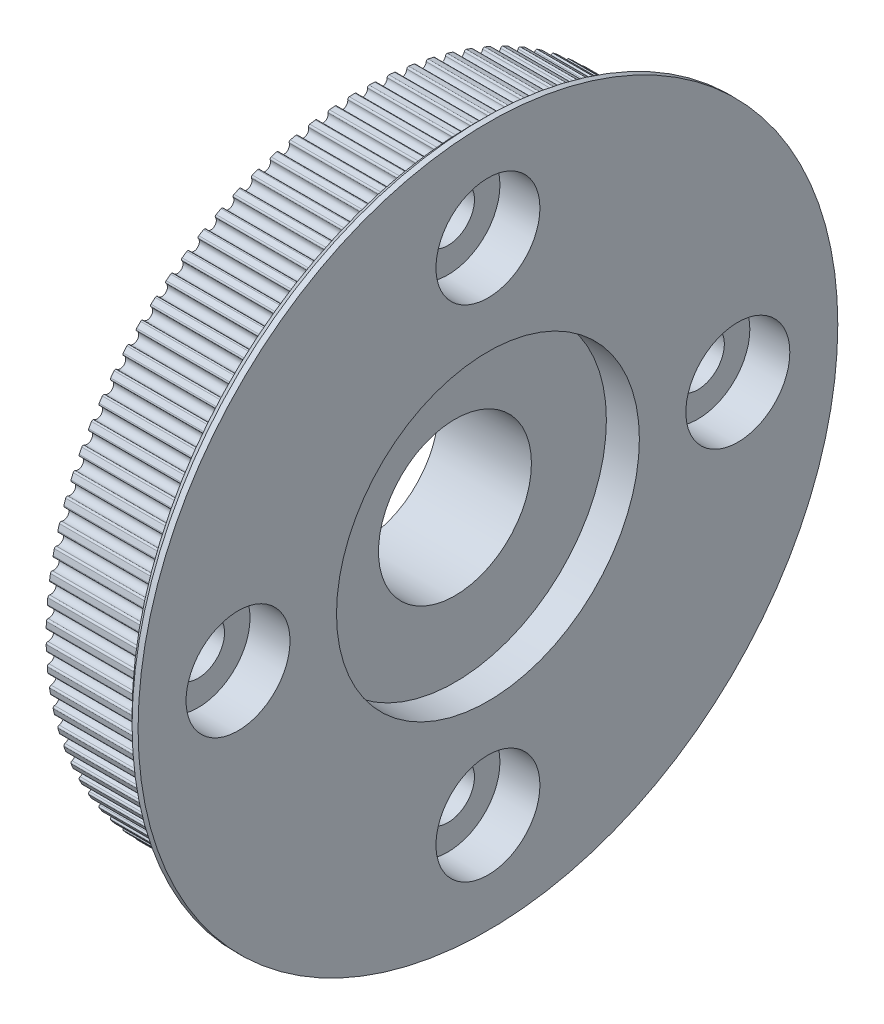
SolidWorks part; units mm, degrees
ref_plane "Front Plane" through (0, 0, 0) normal (0, 0, 1) x (1, 0, 0)
ref_plane "Top Plane" through (0, 0, 0) normal (0, 1, 0) x (1, 0, 0)
ref_plane "Right Plane" through (0, 0, 0) normal (1, 0, 0) x (0, 0, -1)
sketch "Sketch1" plane through (0, 0, 0) normal (1, 0, 0) x (0, 0, -1)
  circle A0 centre (0, 0) radius 31.6
  circle A1 centre (0, 0) radius 7.65
  dimension "D1" = 63.2
  dimension "D2" = 15.3
extrude "Boss-Extrude1" add sketch "Sketch1" along normal blind 11
sketch "Sketch2" plane through (0, 0, 0) normal (1, 0, 0) x (0, 0, -1)
  circle A0 centre (0, 0) radius 31.39 construction
  circle A1 centre (0, 31.39) radius 0.55
  circle A2 centre (0, 0) radius 31.39 construction
  circle A3 centre (1.971, 31.3281) radius 0.55
  circle A4 centre (0, 0) radius 31.39 construction
  circle A5 centre (3.9342, 31.1425) radius 0.55
  circle A6 centre (0, 0) radius 31.39 construction
  circle A7 centre (5.8819, 30.834) radius 0.55
  circle A8 centre (0, 0) radius 31.39 construction
  circle A9 centre (7.8064, 30.4038) radius 0.55
  circle A10 centre (0, 0) radius 31.39 construction
  circle A11 centre (9.7, 29.8537) radius 0.55
  circle A12 centre (0, 0) radius 31.39 construction
  circle A13 centre (11.5554, 29.1857) radius 0.55
  circle A14 centre (0, 0) radius 31.39 construction
  circle A15 centre (13.3652, 28.4025) radius 0.55
  circle A16 centre (0, 0) radius 31.39 construction
  circle A17 centre (15.1222, 27.5073) radius 0.55
  circle A18 centre (0, 0) radius 31.39 construction
  circle A19 centre (16.8196, 26.5035) radius 0.55
  circle A20 centre (0, 0) radius 31.39 construction
  circle A21 centre (18.4506, 25.395) radius 0.55
  circle A22 centre (0, 0) radius 31.39 construction
  circle A23 centre (20.0087, 24.1864) radius 0.55
  circle A24 centre (0, 0) radius 31.39 construction
  circle A25 centre (21.4879, 22.8823) radius 0.55
  circle A26 centre (0, 0) radius 31.39 construction
  circle A27 centre (22.8823, 21.4879) radius 0.55
  circle A28 centre (0, 0) radius 31.39 construction
  circle A29 centre (24.1864, 20.0087) radius 0.55
  circle A30 centre (0, 0) radius 31.39 construction
  circle A31 centre (25.395, 18.4506) radius 0.55
  circle A32 centre (0, 0) radius 31.39 construction
  circle A33 centre (26.5035, 16.8196) radius 0.55
  circle A34 centre (0, 0) radius 31.39 construction
  circle A35 centre (27.5073, 15.1222) radius 0.55
  circle A36 centre (0, 0) radius 31.39 construction
  circle A37 centre (28.4025, 13.3652) radius 0.55
  circle A38 centre (0, 0) radius 31.39 construction
  circle A39 centre (29.1857, 11.5554) radius 0.55
  circle A40 centre (0, 0) radius 31.39 construction
  circle A41 centre (29.8537, 9.7) radius 0.55
  circle A42 centre (0, 0) radius 31.39 construction
  circle A43 centre (30.4038, 7.8064) radius 0.55
  circle A44 centre (0, 0) radius 31.39 construction
  circle A45 centre (30.834, 5.8819) radius 0.55
  circle A46 centre (0, 0) radius 31.39 construction
  circle A47 centre (31.1425, 3.9342) radius 0.55
  circle A48 centre (0, 0) radius 31.39 construction
  circle A49 centre (31.3281, 1.971) radius 0.55
  circle A50 centre (0, 0) radius 31.39 construction
  circle A51 centre (31.39, 0) radius 0.55
  circle A52 centre (0, 0) radius 31.39 construction
  circle A53 centre (31.3281, -1.971) radius 0.55
  circle A54 centre (0, 0) radius 31.39 construction
  circle A55 centre (31.1425, -3.9342) radius 0.55
  circle A56 centre (0, 0) radius 31.39 construction
  circle A57 centre (30.834, -5.8819) radius 0.55
  circle A58 centre (0, 0) radius 31.39 construction
  circle A59 centre (30.4038, -7.8064) radius 0.55
  circle A60 centre (0, 0) radius 31.39 construction
  circle A61 centre (29.8537, -9.7) radius 0.55
  circle A62 centre (0, 0) radius 31.39 construction
  circle A63 centre (29.1857, -11.5554) radius 0.55
  circle A64 centre (0, 0) radius 31.39 construction
  circle A65 centre (28.4025, -13.3652) radius 0.55
  circle A66 centre (0, 0) radius 31.39 construction
  circle A67 centre (27.5073, -15.1222) radius 0.55
  circle A68 centre (0, 0) radius 31.39 construction
  circle A69 centre (26.5035, -16.8196) radius 0.55
  circle A70 centre (0, 0) radius 31.39 construction
  circle A71 centre (25.395, -18.4506) radius 0.55
  circle A72 centre (0, 0) radius 31.39 construction
  circle A73 centre (24.1864, -20.0087) radius 0.55
  circle A74 centre (0, 0) radius 31.39 construction
  circle A75 centre (22.8823, -21.4879) radius 0.55
  circle A76 centre (0, 0) radius 31.39 construction
  circle A77 centre (21.4879, -22.8823) radius 0.55
  circle A78 centre (0, 0) radius 31.39 construction
  circle A79 centre (20.0087, -24.1864) radius 0.55
  circle A80 centre (0, 0) radius 31.39 construction
  circle A81 centre (18.4506, -25.395) radius 0.55
  circle A82 centre (0, 0) radius 31.39 construction
  circle A83 centre (16.8196, -26.5035) radius 0.55
  circle A84 centre (0, 0) radius 31.39 construction
  circle A85 centre (15.1222, -27.5073) radius 0.55
  circle A86 centre (0, 0) radius 31.39 construction
  circle A87 centre (13.3652, -28.4025) radius 0.55
  circle A88 centre (0, 0) radius 31.39 construction
  circle A89 centre (11.5554, -29.1857) radius 0.55
  circle A90 centre (0, 0) radius 31.39 construction
  circle A91 centre (9.7, -29.8537) radius 0.55
  circle A92 centre (0, 0) radius 31.39 construction
  circle A93 centre (7.8064, -30.4038) radius 0.55
  circle A94 centre (0, 0) radius 31.39 construction
  circle A95 centre (5.8819, -30.834) radius 0.55
  circle A96 centre (0, 0) radius 31.39 construction
  circle A97 centre (3.9342, -31.1425) radius 0.55
  circle A98 centre (0, 0) radius 31.39 construction
  circle A99 centre (1.971, -31.3281) radius 0.55
  circle A100 centre (0, 0) radius 31.39 construction
  circle A101 centre (0, -31.39) radius 0.55
  circle A102 centre (0, 0) radius 31.39 construction
  circle A103 centre (-1.971, -31.3281) radius 0.55
  circle A104 centre (0, 0) radius 31.39 construction
  circle A105 centre (-3.9342, -31.1425) radius 0.55
  circle A106 centre (0, 0) radius 31.39 construction
  circle A107 centre (-5.8819, -30.834) radius 0.55
  circle A108 centre (0, 0) radius 31.39 construction
  circle A109 centre (-7.8064, -30.4038) radius 0.55
  circle A110 centre (0, 0) radius 31.39 construction
  circle A111 centre (-9.7, -29.8537) radius 0.55
  circle A112 centre (0, 0) radius 31.39 construction
  circle A113 centre (-11.5554, -29.1857) radius 0.55
  circle A114 centre (0, 0) radius 31.39 construction
  circle A115 centre (-13.3652, -28.4025) radius 0.55
  circle A116 centre (0, 0) radius 31.39 construction
  circle A117 centre (-15.1222, -27.5073) radius 0.55
  circle A118 centre (0, 0) radius 31.39 construction
  circle A119 centre (-16.8196, -26.5035) radius 0.55
  circle A120 centre (0, 0) radius 31.39 construction
  circle A121 centre (-18.4506, -25.395) radius 0.55
  circle A122 centre (0, 0) radius 31.39 construction
  circle A123 centre (-20.0087, -24.1864) radius 0.55
  circle A124 centre (0, 0) radius 31.39 construction
  circle A125 centre (-21.4879, -22.8823) radius 0.55
  circle A126 centre (0, 0) radius 31.39 construction
  circle A127 centre (-22.8823, -21.4879) radius 0.55
  circle A128 centre (0, 0) radius 31.39 construction
  circle A129 centre (-24.1864, -20.0087) radius 0.55
  circle A130 centre (0, 0) radius 31.39 construction
  circle A131 centre (-25.395, -18.4506) radius 0.55
  circle A132 centre (0, 0) radius 31.39 construction
  circle A133 centre (-26.5035, -16.8196) radius 0.55
  circle A134 centre (0, 0) radius 31.39 construction
  circle A135 centre (-27.5073, -15.1222) radius 0.55
  circle A136 centre (0, 0) radius 31.39 construction
  circle A137 centre (-28.4025, -13.3652) radius 0.55
  circle A138 centre (0, 0) radius 31.39 construction
  circle A139 centre (-29.1857, -11.5554) radius 0.55
  circle A140 centre (0, 0) radius 31.39 construction
  circle A141 centre (-29.8537, -9.7) radius 0.55
  circle A142 centre (0, 0) radius 31.39 construction
  circle A143 centre (-30.4038, -7.8064) radius 0.55
  circle A144 centre (0, 0) radius 31.39 construction
  circle A145 centre (-30.834, -5.8819) radius 0.55
  circle A146 centre (0, 0) radius 31.39 construction
  circle A147 centre (-31.1425, -3.9342) radius 0.55
  circle A148 centre (0, 0) radius 31.39 construction
  circle A149 centre (-31.3281, -1.971) radius 0.55
  circle A150 centre (0, 0) radius 31.39 construction
  circle A151 centre (-31.39, 0) radius 0.55
  circle A152 centre (0, 0) radius 31.39 construction
  circle A153 centre (-31.3281, 1.971) radius 0.55
  circle A154 centre (0, 0) radius 31.39 construction
  circle A155 centre (-31.1425, 3.9342) radius 0.55
  circle A156 centre (0, 0) radius 31.39 construction
  circle A157 centre (-30.834, 5.8819) radius 0.55
  circle A158 centre (0, 0) radius 31.39 construction
  circle A159 centre (-30.4038, 7.8064) radius 0.55
  circle A160 centre (0, 0) radius 31.39 construction
  circle A161 centre (-29.8537, 9.7) radius 0.55
  circle A162 centre (0, 0) radius 31.39 construction
  circle A163 centre (-29.1857, 11.5554) radius 0.55
  circle A164 centre (0, 0) radius 31.39 construction
  circle A165 centre (-28.4025, 13.3652) radius 0.55
  circle A166 centre (0, 0) radius 31.39 construction
  circle A167 centre (-27.5073, 15.1222) radius 0.55
  circle A168 centre (0, 0) radius 31.39 construction
  circle A169 centre (-26.5035, 16.8196) radius 0.55
  circle A170 centre (0, 0) radius 31.39 construction
  circle A171 centre (-25.395, 18.4506) radius 0.55
  circle A172 centre (0, 0) radius 31.39 construction
  circle A173 centre (-24.1864, 20.0087) radius 0.55
  circle A174 centre (0, 0) radius 31.39 construction
  circle A175 centre (-22.8823, 21.4879) radius 0.55
  circle A176 centre (0, 0) radius 31.39 construction
  circle A177 centre (-21.4879, 22.8823) radius 0.55
  circle A178 centre (0, 0) radius 31.39 construction
  circle A179 centre (-20.0087, 24.1864) radius 0.55
  circle A180 centre (0, 0) radius 31.39 construction
  circle A181 centre (-18.4506, 25.395) radius 0.55
  circle A182 centre (0, 0) radius 31.39 construction
  circle A183 centre (-16.8196, 26.5035) radius 0.55
  circle A184 centre (0, 0) radius 31.39 construction
  circle A185 centre (-15.1222, 27.5073) radius 0.55
  circle A186 centre (0, 0) radius 31.39 construction
  circle A187 centre (-13.3652, 28.4025) radius 0.55
  circle A188 centre (0, 0) radius 31.39 construction
  circle A189 centre (-11.5554, 29.1857) radius 0.55
  circle A190 centre (0, 0) radius 31.39 construction
  circle A191 centre (-9.7, 29.8537) radius 0.55
  circle A192 centre (0, 0) radius 31.39 construction
  circle A193 centre (-7.8064, 30.4038) radius 0.55
  circle A194 centre (0, 0) radius 31.39 construction
  circle A195 centre (-5.8819, 30.834) radius 0.55
  circle A196 centre (0, 0) radius 31.39 construction
  circle A197 centre (-3.9342, 31.1425) radius 0.55
  circle A198 centre (0, 0) radius 31.39 construction
  circle A199 centre (-1.971, 31.3281) radius 0.55
  point P305 (0, 0)
  dimension "D1" = 62.78
  dimension "D2" = 1.1
  dimension "D3" = 100
extrude "Cut-Extrude1" cut sketch "Sketch2" along normal up to surface (11 mm away) up to face at (11, 0, -31.6)
fillet "Fillet1" radius 0.16 200 edges at (5.5, 31.5959, 0.51) (5.5, 31.5656, 1.4749) (5.5, 21.2571, -23.3815) (5.5, 22.6833, -22.0007) (5.5, 22.0007, -22.6833) (5.5, 20.5329, -24.02) (5.5, 19.747, -24.6701) (5.5, 18.9842, -25.2618) (5.5, 18.159, -25.8614) (5.5, 17.3605, -26.404) (5.5, 16.4993, -26.9506) (5.5, 15.6684, -27.442) (5.5, 14.7745, -27.9334) (5.5, 13.9143, -28.3717) (5.5, 12.9914, -28.806) (5.5, 12.1054, -29.1894) (5.5, 23.3815, -21.2571) (5.5, 24.02, -20.5329) (5.5, 24.6701, -19.747) (5.5, 25.2618, -18.9842) (5.5, 25.8614, -18.159) (5.5, 26.404, -17.3605) (5.5, 26.9506, -16.4993) (5.5, 27.442, -15.6684) (5.5, 27.9334, -14.7745) (5.5, 28.3717, -13.9143) (5.5, 28.806, -12.9914) (5.5, 29.1894, -12.1054) (5.5, 29.5649, -11.157) (5.5, 29.8919, -10.2487) (5.5, 30.2071, -9.2786) (5.5, 30.4764, -8.3516) (5.5, 30.7301, -7.3636) (5.5, 30.9407, -6.4215) (5.5, 31.1318, -5.4195) (5.5, 31.2828, -4.466) (5.5, 31.4107, -3.454) (5.5, 31.5015, -2.4929) (5.5, 31.5656, -1.4749) (5.5, 31.5959, -0.51) (5.5, 31.5015, 2.4929) (5.5, 31.4107, 3.454) (5.5, 31.2828, 4.466) (5.5, 31.1318, 5.4195) (5.5, 30.9407, 6.4215) (5.5, 30.7301, 7.3636) (5.5, 30.4764, 8.3516) (5.5, 30.2071, 9.2786) (5.5, 29.8919, 10.2487) (5.5, 29.5649, 11.157) (5.5, 29.1894, 12.1054) (5.5, 28.806, 12.9914) (5.5, 28.3717, 13.9143) (5.5, 27.9334, 14.7745) (5.5, 27.442, 15.6684) (5.5, 26.9506, 16.4993) (5.5, 26.404, 17.3605) (5.5, 25.8614, 18.159) (5.5, 25.2618, 18.9842) (5.5, 24.6701, 19.747) (5.5, 24.02, 20.5329) (5.5, 23.3815, 21.2571) (5.5, 22.6833, 22.0007) (5.5, 22.0007, 22.6833) (5.5, 21.2571, 23.3815) (5.5, 20.5329, 24.02) (5.5, 19.747, 24.6701) (5.5, 18.9842, 25.2618) (5.5, 18.159, 25.8614) (5.5, 17.3605, 26.404) (5.5, 16.4993, 26.9506) (5.5, 15.6684, 27.442) (5.5, 14.7745, 27.9334) (5.5, 13.9143, 28.3717) (5.5, 12.9914, 28.806) (5.5, 12.1054, 29.1894) (5.5, 11.157, 29.5649) (5.5, 10.2487, 29.8919) (5.5, 9.2786, 30.2071) (5.5, 8.3516, 30.4764) (5.5, 7.3636, 30.7301) (5.5, 6.4215, 30.9407) (5.5, 5.4195, 31.1318) (5.5, 4.466, 31.2828) (5.5, 3.454, 31.4107) (5.5, 2.4929, 31.5015) (5.5, 1.4749, 31.5656) (5.5, 0.51, 31.5959) (5.5, -0.51, 31.5959) (5.5, -1.4749, 31.5656) (5.5, -2.4929, 31.5015) (5.5, -3.454, 31.4107) (5.5, -4.466, 31.2828) (5.5, -5.4195, 31.1318) (5.5, -6.4215, 30.9407) (5.5, -7.3636, 30.7301) (5.5, -8.3516, 30.4764) (5.5, -9.2786, 30.2071) (5.5, -10.2487, 29.8919) (5.5, -11.157, 29.5649) (5.5, -12.1054, 29.1894) (5.5, -12.9914, 28.806) (5.5, -13.9143, 28.3717) (5.5, -14.7745, 27.9334) (5.5, -15.6684, 27.442) (5.5, -16.4993, 26.9506) (5.5, -17.3605, 26.404) (5.5, -18.159, 25.8614) (5.5, -18.9842, 25.2618) (5.5, -19.747, 24.6701) (5.5, -20.5329, 24.02) (5.5, -21.2571, 23.3815) (5.5, -22.0007, 22.6833) (5.5, -22.6833, 22.0007) (5.5, -23.3815, 21.2571) (5.5, -24.02, 20.5329) (5.5, -24.6701, 19.747) (5.5, -25.2618, 18.9842) (5.5, -25.8614, 18.159) (5.5, -26.404, 17.3605) (5.5, -26.9506, 16.4993) (5.5, -27.442, 15.6684) (5.5, -27.9334, 14.7745) (5.5, -28.3717, 13.9143) (5.5, -28.806, 12.9914) (5.5, -29.1894, 12.1054) (5.5, -29.5649, 11.157) (5.5, -29.8919, 10.2487) (5.5, -30.2071, 9.2786) (5.5, -30.4764, 8.3516) (5.5, -30.7301, 7.3636) (5.5, -30.9407, 6.4215) (5.5, -31.1318, 5.4195) (5.5, -31.2828, 4.466) (5.5, -31.4107, 3.454) (5.5, -31.5015, 2.4929) (5.5, -31.5656, 1.4749) (5.5, -31.5959, 0.51) (5.5, -31.5959, -0.51) (5.5, -31.5656, -1.4749) (5.5, -31.5015, -2.4929) (5.5, -31.4107, -3.454) (5.5, -31.2828, -4.466) (5.5, -31.1318, -5.4195) (5.5, -30.9407, -6.4215) (5.5, -30.7301, -7.3636) (5.5, -30.4764, -8.3516) (5.5, -30.2071, -9.2786) (5.5, -29.8919, -10.2487) (5.5, -29.5649, -11.157) (5.5, -29.1894, -12.1054) (5.5, -28.806, -12.9914) (5.5, -28.3717, -13.9143) (5.5, -27.9334, -14.7745) (5.5, -27.442, -15.6684) (5.5, -26.9506, -16.4993) (5.5, -26.404, -17.3605) (5.5, -25.8614, -18.159) (5.5, -25.2618, -18.9842) (5.5, -24.6701, -19.747) (5.5, -24.02, -20.5329) (5.5, -23.3815, -21.2571) (5.5, -22.6833, -22.0007) (5.5, -22.0007, -22.6833) (5.5, -21.2571, -23.3815) (5.5, -20.5329, -24.02) (5.5, -19.747, -24.6701) (5.5, -18.9842, -25.2618) (5.5, -18.159, -25.8614) (5.5, -17.3605, -26.404) (5.5, -16.4993, -26.9506) (5.5, -15.6684, -27.442) (5.5, -14.7745, -27.9334) (5.5, -13.9143, -28.3717) (5.5, -12.9914, -28.806) (5.5, -12.1054, -29.1894) (5.5, -11.157, -29.5649) (5.5, -10.2487, -29.8919) (5.5, -9.2786, -30.2071) (5.5, -8.3516, -30.4764) (5.5, -7.3636, -30.7301) (5.5, -6.4215, -30.9407) (5.5, -5.4195, -31.1318) (5.5, -4.466, -31.2828) (5.5, -3.454, -31.4107) (5.5, -2.4929, -31.5015) (5.5, 11.157, -29.5649) (5.5, 10.2487, -29.8919) (5.5, 9.2786, -30.2071) (5.5, 8.3516, -30.4764) (5.5, 7.3636, -30.7301) (5.5, 6.4215, -30.9407) (5.5, 5.4195, -31.1318) (5.5, 4.466, -31.2828) (5.5, 3.454, -31.4107) (5.5, 2.4929, -31.5015) (5.5, 1.4749, -31.5656) (5.5, 0.51, -31.5959) (5.5, -1.4749, -31.5656) (5.5, -0.51, -31.5959)
sketch "Sketch3" plane through (11, 0, 0) normal (1, 0, 0) x (0, 0, -1)
  circle A0 centre (0, 0) radius 35
  circle A1 centre (0, 0) radius 7.65
  circle A2 centre (0, 0) radius 7.65 construction
  dimension "D1" = 70
extrude "Boss-Extrude2" add sketch "Sketch3" along normal blind 1.6
chamfer "Chamfer1" distance 1 angle 45 1 edges at (11, 0, -35)
sketch "Sketch8" plane through (12.6, 0, 0) normal (1, 0, 0) x (0, 0, -1)
  circle A0 centre (0, 0) radius 15.15
  dimension "D1" = 30.3
extrude "Cut-Extrude7" cut sketch "Sketch8" against normal blind 3.3
sketch "Croquis2" plane through (9.3, 0, 0) normal (1, 0, 0) x (0, 0, -1)
  circle A0 centre (0, 0) radius 15.15
  dimension "D1" = 30.3
extrude "Saliente-Extruir1" add sketch "Croquis2" against normal up to vertex (9.3 mm away) up to point (0, -21.1069, -23.5172)
sketch "Croquis3" plane through (9.3, 0, 0) normal (1, 0, 0) x (0, 0, -1)
  circle A0 centre (0, 0) radius 7.65
  dimension "D1" = 15.3
extrude "Cortar-Extruir1" cut sketch "Croquis3" against normal through all
sketch "Croquis6" plane through (12.6, 0, 0) normal (1, 0, 0) x (0, 0, -1)
  line L0 (0, 0) -> (0, -25) construction
  line L1 (0, 0) -> (25, 0) construction
  line L2 (0, 0) -> (-25, 0) construction
  line L3 (0, 0) -> (0, 25) construction
  circle A0 centre (0, -25) radius 5.2
  circle A1 centre (25, 0) radius 5.2
  circle A2 centre (-25, 0) radius 5.2
  circle A3 centre (0, 25) radius 5.2
  dimension "D5" = 10.4
  dimension "D1" = 25
  dimension "D2" = 25
  dimension "D3" = 25
  dimension "D4" = 25
extrude "Cortar-Extruir2" cut sketch "Croquis6" against normal blind 4
sketch "Croquis7" plane through (8.6, 0, 0) normal (1, 0, 0) x (0, 0, -1)
  circle A0 centre (0, -25) radius 2.65
  dimension "D1" = 5.3
extrude "Cortar-Extruir3" cut sketch "Croquis7" against normal through all
sketch "Croquis8" plane through (8.6, 0, 0) normal (1, 0, 0) x (0, 0, -1)
  circle A0 centre (-25, 0) radius 2.65
  dimension "D1" = 5.3
extrude "Cortar-Extruir4" cut sketch "Croquis8" against normal through all
sketch "Croquis9" plane through (8.6, 0, 0) normal (1, 0, 0) x (0, 0, -1)
  circle A0 centre (25, 0) radius 2.65
  dimension "D1" = 5.3
extrude "Cortar-Extruir5" cut sketch "Croquis9" against normal through all
sketch "Croquis10" plane through (8.6, 0, 0) normal (1, 0, 0) x (0, 0, -1)
  circle A0 centre (0, 25) radius 2.65
  dimension "D1" = 5.3
extrude "Cortar-Extruir6" cut sketch "Croquis10" against normal through all
